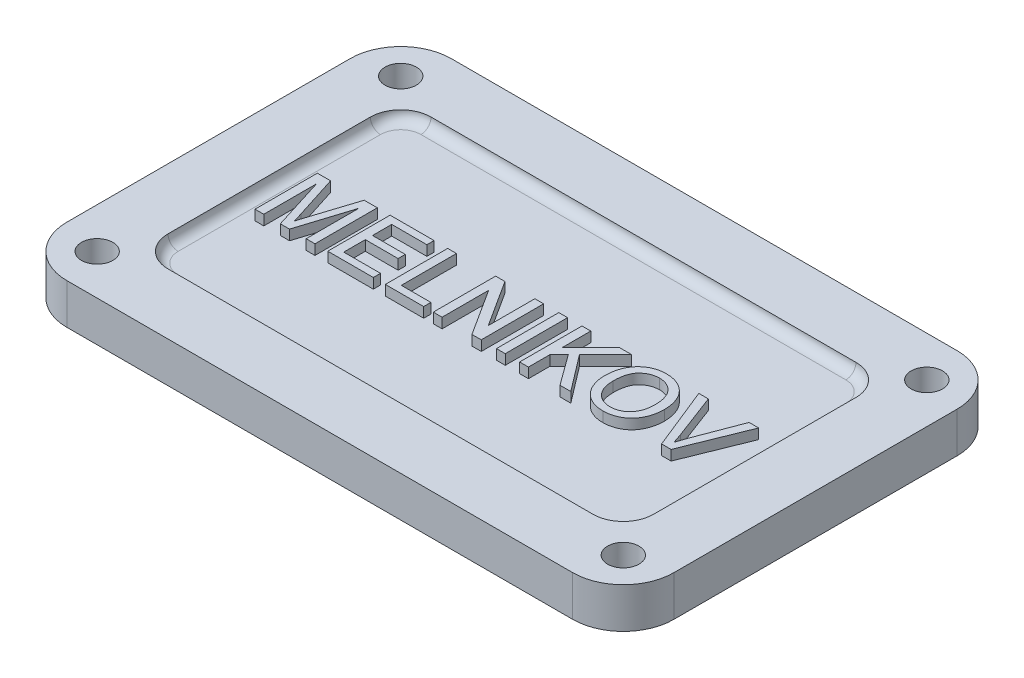
SolidWorks part; units mm, degrees
ref_plane "Спереди" through (0, 0, 0) normal (0, 0, 1) x (1, 0, 0)
ref_plane "Сверху" through (0, 0, 0) normal (0, 1, 0) x (1, 0, 0)
ref_plane "Справа" through (0, 0, 0) normal (1, 0, 0) x (0, 0, -1)
sketch "Эскиз1" plane through (0, 0, 0) normal (0, 1, 0) x (1, 0, 0)
  line L1 (0, 0) -> (120, 0)
  line L2 (0, 0) -> (0, 76)
  line L3 (0, 76) -> (120, 76)
  line L4 (120, 0) -> (120, 76)
  dimension "D1" = 120
  dimension "D2" = 76
extrude "Бобышка-Вытянуть1" add sketch "Эскиз1" along normal blind 8
fillet "Скругление1" radius 10 4 edges at (120, 4, 0) (120, 4, -76) (0, 4, -76) (0, 4, 0)
sketch "Эскиз2" plane through (0, 8, 0) normal (0, 1, 0) x (1, 0, 0)
  line L0 (0, 66) -> (0, 10) construction
  line L1 (12, 64) -> (108, 64)
  line L2 (12, 64) -> (12, 12)
  line L3 (12, 12) -> (108, 12)
  line L4 (108, 64) -> (108, 12)
  line L5 (120, 10) -> (120, 66) construction
  line L6 (110, 76) -> (10, 76) construction
  line L7 (10, 0) -> (110, 0) construction
  dimension "D1" = 12
  dimension "D2" = 12
  dimension "D3" = 12
  dimension "D4" = 12
extrude "Вырез-Вытянуть1" cut sketch "Эскиз2" against normal blind 2
fillet "Скругление2" radius 6 4 edges at (108, 7, -64) (108, 7, -12) (12, 7, -12) (12, 7, -64)
sketch "Эскиз3" plane through (0, 8, 0) normal (0, 1, 0) x (1, 0, 0)
  line L0 (0, 66) -> (0, 10) construction
  line L1 (110, 76) -> (10, 76) construction
  line L2 (120, 10) -> (120, 66) construction
  line L3 (10, 0) -> (110, 0) construction
  circle A0 centre (8, 68) radius 3.1
  circle A1 centre (112, 68) radius 3.1
  circle A2 centre (112, 8) radius 3.1
  circle A3 centre (8, 8) radius 3.1
  point P18 (0.4002, 7.1992)
  dimension "D1" = 8
  dimension "D2" = 8
  dimension "D3" = 8
  dimension "D4" = 8
  dimension "D5" = 8
  dimension "D6" = 8
  dimension "D7" = 8
  dimension "D8" = 8
extrude "Вырез-Вытянуть2" cut sketch "Эскиз3" against normal blind 32
sketch "Эскиз4" plane through (0, 6, 0) normal (0, 1, 0) x (1, 0, 0)
  text T0 "MELNIKOV" font "Arial" height in points 48
  point P1 (0, 0)
extrude "Бобышка-Вытянуть2" add sketch "Эскиз4" along normal blind 2
sketch "Эскиз5" plane through (0, 0, 0) normal (0, -1, 0) x (1, 0, 0)
  line L0 (0, -66) -> (0, -10) construction
  line L1 (12, -12) -> (108, -12)
  line L2 (12, -12) -> (12, -64)
  line L3 (12, -64) -> (108, -64)
  line L4 (108, -12) -> (108, -64)
  line L5 (120, -10) -> (120, -66) construction
  line L6 (10, 0) -> (110, 0) construction
  line L7 (110, -76) -> (10, -76) construction
  dimension "D1" = 12
  dimension "D2" = 12
  dimension "D3" = 12
  dimension "D4" = 12
extrude "Вырез-Вытянуть3" cut sketch "Эскиз5" against normal blind 2
fillet "Скругление3" radius 6 4 edges at (108, 1, -12) (108, 1, -64) (12, 1, -64) (12, 1, -12)
fillet "Скругление8" radius 2 16 edges at (106.2426, 6, -62.2426) (13.7574, 6, -13.7574) (60, 6, -12) (106.2426, 6, -13.7574) (108, 6, -38) (60, 6, -64) (12, 6, -38) (13.7574, 6, -62.2426) (13.7574, 2, -62.2426) (60, 2, -64) (12, 2, -38) (106.2426, 2, -62.2426) (108, 2, -38) (106.2426, 2, -13.7574) (60, 2, -12) (13.7574, 2, -13.7574)
